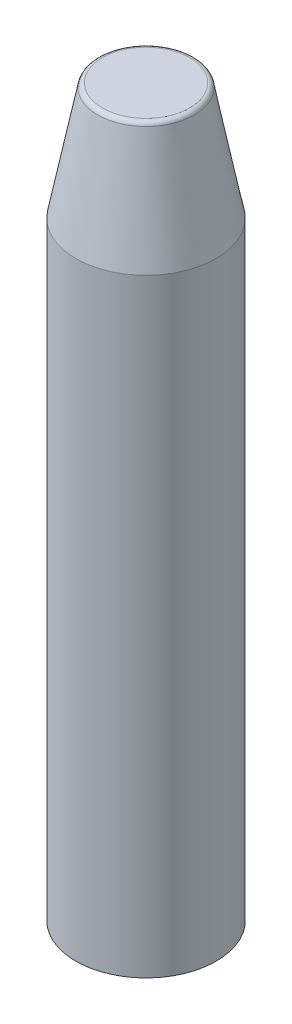
SolidWorks part; units mm, degrees
ref_plane "Alzado" through (0, 0, 0) normal (0, 0, 1) x (1, 0, 0)
ref_plane "Planta" through (0, 0, 0) normal (0, 1, 0) x (1, 0, 0)
ref_plane "Vista lateral" through (0, 0, 0) normal (1, 0, 0) x (0, 0, -1)
sketch "Croquis1" plane through (0, 0, 0) normal (0, 1, 0) x (1, 0, 0)
  circle A0 centre (0, 0) radius 3
  dimension "D1" = 6
extrude "Saliente-Extruir1" add sketch "Croquis1" along normal blind 26
sketch "Croquis2" plane through (0, 26, 0) normal (0, 1, 0) x (1, 0, 0)
  circle A1 centre (0, 0) radius 3
  circle A2 centre (0, 0) radius 3
  dimension "D1" = 0
extrude "Saliente-Extruir2" add sketch "Croquis2" along normal blind 5 draft 11
fillet "Redondeo1" radius 0.2 1 edges at (0, 31, 2.0281)
sketch "Croquis5" plane through (0, 0, 0) normal (0, -1, 0) x (1, 0, 0)
  circle A0 centre (0, 0) radius 1.5
  dimension "D1" = 3
extrude "Cortar-Extruir1" cut sketch "Croquis5" against normal blind 9
thread "Rosca1" pitch 0.5 method extrude profile "Perfil de rosca1" start angle 0, offset 2, length 8, pitch 0.5, diameter 3
ref_plane "Plano1" through (1.5, -2, 0) normal (0, 0, 1) x (1, 0, 0)
sketch "Perfil de rosca1" plane through (1.5, -2, 0) normal (0, 0, 1) x (1, 0, 0)
  line L0 (0, 0) -> (0, 0.5) construction
  line L11 (0, 0) -> (0, 0.4375)
  line L12 (0, 0.4375) -> (-0.2706, 0.2812)
  line L13 (-0.2706, 0.2812) -> (-0.2706, 0.1562)
  line L15 (-0.2706, 0.1562) -> (0, 0)
  line L17 (-0.2706, 0.2187) -> (0, 0.2187) construction
  point P2 (0, 0)
  dimension "Pitch" = 0.5
  dimension "Profile_Angle" = 60
  dimension "Profile_Land" = 0.125
  dimension "Profile_Height" = 0.2706
sketch "Croquis8" plane through (0, 0, 0) normal (0, -1, 0) x (1, 0, 0)
  circle A0 centre (0, 0) radius 3
extrude "Cortar-Extruir2" cut sketch "Croquis8" along normal blind 9
